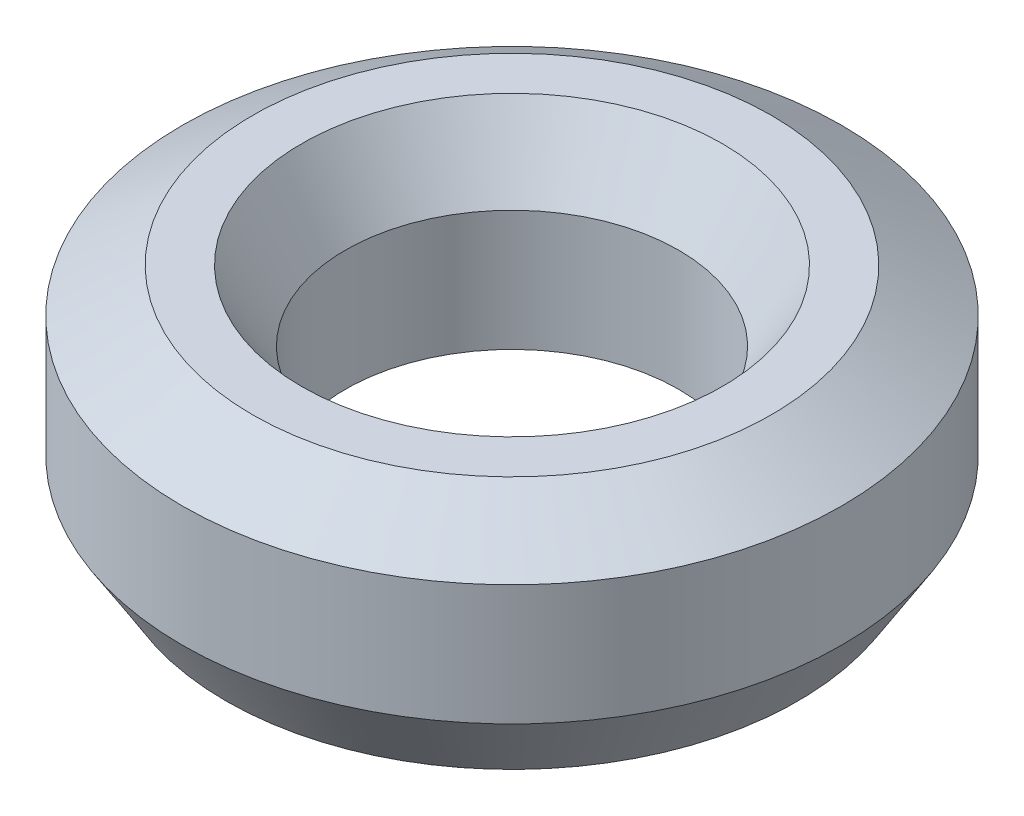
SolidWorks part; units mm, degrees
ref_plane "Front Plane" through (0, 0, 0) normal (0, 0, 1) x (1, 0, 0)
ref_plane "Top Plane" through (0, 0, 0) normal (0, 1, 0) x (1, 0, 0)
ref_plane "Right Plane" through (0, 0, 0) normal (1, 0, 0) x (0, 0, -1)
sketch "Sketch1" plane through (0, 0, 0) normal (0, 1, 0) x (1, 0, 0)
  circle A0 centre (0, 0) radius 27.5
  dimension "SLEEVE_OD" = 55
extrude "Boss-Extrude1" add sketch "Sketch1" along normal blind 19.5688
sketch "Sketch2" plane through (0, 0, 0) normal (0, 1, 0) x (1, 0, 0)
  circle A0 centre (0, 0) radius 13.8977
  dimension "BORE_D" = 27.7953
extrude "Cut-Extrude1" cut sketch "Sketch2" along normal through all
chamfer "Chamfer1" distance 3.65 angle 58.104 4 edges at (0, 19.5688, 13.8977) (0, 0, 13.8977) (0, 0, 27.5) (0, 19.5688, 27.5) first distance on face at (0, 19.5688, 13.8977) first distance on face at (0, 0, 13.8977) first distance on face at (0, 19.5688, 27.5)
